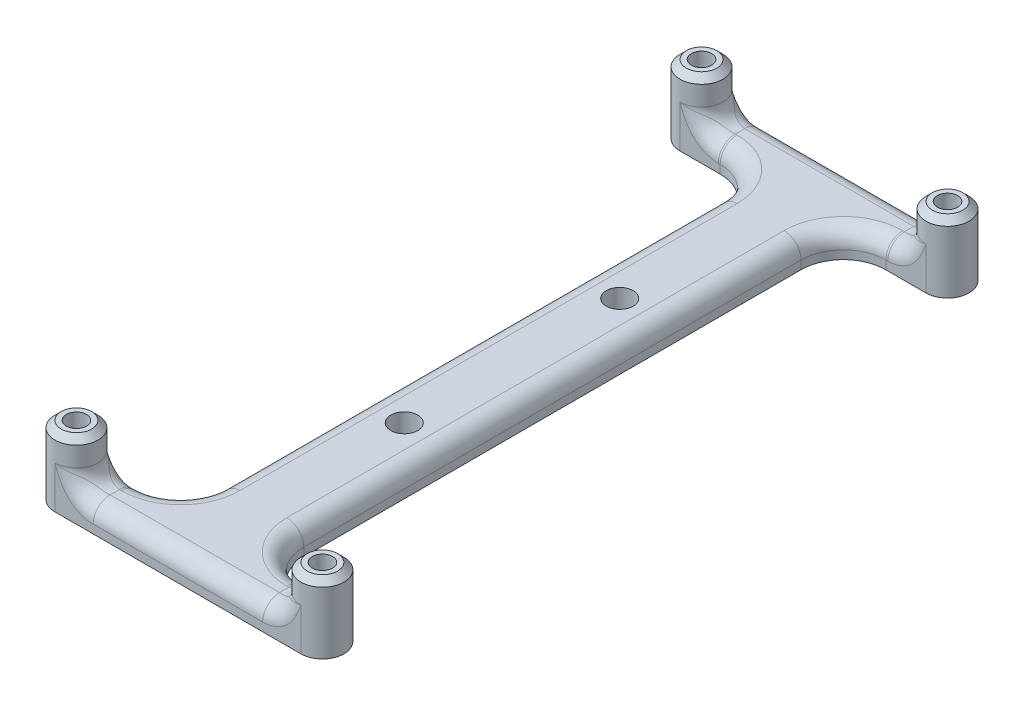
SolidWorks part; units mm, degrees
ref_plane "Front Plane" through (0, 0, 0) normal (0, 0, 1) x (1, 0, 0)
ref_plane "Top Plane" through (0, 0, 0) normal (0, 1, 0) x (1, 0, 0)
ref_plane "Right Plane" through (0, 0, 0) normal (1, 0, 0) x (0, 0, -1)
sketch "Sketch1" plane through (0, 0, 0) normal (0, 1, 0) x (1, 0, 0)
  line L1 (-4.7625, -34.305) -> (4.7625, -34.305)
  line L2 (-4.7625, -34.305) -> (-4.7625, 34.305)
  line L3 (-4.7625, 34.305) -> (4.7625, 34.305)
  line L4 (4.7625, -34.305) -> (4.7625, 34.305)
  line L5 (-4.7625, -34.305) -> (4.7625, 34.305) construction
  line L6 (-4.7625, 34.305) -> (4.7625, -34.305) construction
  line L7 (-14.5, 39.385) -> (14.5, 39.385)
  line L9 (-14.5, 34.305) -> (14.5, 34.305)
  line L11 (-14.5, 39.385) -> (14.5, 34.305) construction
  line L12 (-14.5, 34.305) -> (14.5, 39.385) construction
  line L13 (-14.5, -39.385) -> (14.5, -39.385)
  line L15 (-14.5, -34.305) -> (14.5, -34.305)
  line L17 (-14.5, -39.385) -> (14.5, -34.305) construction
  line L18 (-14.5, -34.305) -> (14.5, -39.385) construction
  arc A2 (-14.5, 34.305) -> (-14.5, 39.385) centre (-14.5, 36.845) cw
  arc A3 (14.5, 34.305) -> (14.5, 39.385) centre (14.5, 36.845) ccw
  arc A4 (-14.5, -39.385) -> (-14.5, -34.305) centre (-14.5, -36.845) cw
  arc A5 (14.5, -39.385) -> (14.5, -34.305) centre (14.5, -36.845) ccw
  point P0 (0, 0)
  point P6 (0, 36.845)
  point P11 (0, -36.845)
  point P17 (0, 0)
  point P18 (0, 0)
  point P19 (-14.1971, 41.0601)
  point P24 (13.1626, -36.2976)
  point P25 (0, 0)
  point P26 (13.1626, 40.1254)
  dimension "D4" = 29
  dimension "D1" = 9.525
  dimension "D2" = 5.08
  dimension "D3" = 5.08
  dimension "D5" = 73.69
extrude "Boss-Extrude1" add sketch "Sketch1" along normal blind 3 contours L13 A5 L15 L1 A4 | L1 L4 L3 L2 | L9 A3 L7 A2 L3 region at (0, 0, 0) region at (0, 0, 36.845) region at (0, 0, -36.845)
sketch "Sketch2" plane through (0, 3, 0) normal (0, 1, 0) x (1, 0, 0)
  line L0 (0, 12.7) -> (0, -12.7) construction
  circle A0 centre (0, 12.7) radius 1.5875
  circle A1 centre (0, -12.7) radius 1.5875
  dimension "D2" = 3.175
  dimension "D3" = 3.175
  dimension "D1" = 25.4
extrude "Cut-Extrude1" cut sketch "Sketch2" against normal through all
sketch "Sketch3" plane through (0, 3, 0) normal (0, 1, 0) x (1, 0, 0)
  circle A0 centre (-14.5, 36.845) radius 2.54
  circle A1 centre (14.5, 36.845) radius 2.54
  circle A2 centre (14.5, -36.845) radius 2.54
  circle A3 centre (-14.5, -36.845) radius 2.54
  arc A4 (-14.5, 39.385) -> (-14.5, 34.305) centre (-14.5, 36.845) ccw construction
  arc A5 (14.5, 34.305) -> (14.5, 39.385) centre (14.5, 36.845) ccw construction
  arc A6 (-14.5, -34.305) -> (-14.5, -39.385) centre (-14.5, -36.845) ccw construction
  arc A7 (14.5, -39.385) -> (14.5, -34.305) centre (14.5, -36.845) ccw construction
extrude "Boss-Extrude2" add sketch "Sketch3" along normal blind 5.08
sketch "Sketch4" plane through (0, 8.08, 0) normal (0, 1, 0) x (1, 0, 0)
  circle A0 centre (-14.5, 36.845) radius 1.1938
  circle A1 centre (14.5, 36.845) radius 1.1938
  circle A2 centre (14.5, -36.845) radius 1.1938
  circle A3 centre (-14.5, -36.845) radius 1.1938
  dimension "D1" = 2.3876
  dimension "D2" = 2.3876
  dimension "D3" = 2.3876
  dimension "D4" = 2.3876
extrude "Cut-Extrude2" cut sketch "Sketch4" against normal blind 3.2004
sketch "Sketch5" plane through (0, 4.8796, 0) normal (0, 1, 0) x (1, 0, 0)
  circle A0 centre (-14.5, 36.845) radius 0.875
  circle A1 centre (14.5, 36.845) radius 0.875
  circle A2 centre (14.5, -36.845) radius 0.875
  circle A3 centre (-14.5, -36.845) radius 0.875
  dimension "D1" = 1.75
  dimension "D2" = 1.75
  dimension "D3" = 1.75
  dimension "D4" = 1.75
extrude "Cut-Extrude3" cut sketch "Sketch5" against normal through all
chamfer "Chamfer1" distance 0.75 angle 45 4 edges at (-14.5, 8.08, -34.305) (14.5, 8.08, -34.305) (14.5, 8.08, 39.385) (-14.5, 8.08, 39.385)
fillet "Fillet1" radius 5 4 edges at (-4.7625, 1.5, -34.305) (4.7625, 1.5, -34.305) (-4.7625, 1.5, 34.305) (4.7625, 1.5, 34.305)
fillet "Fillet2" radius 2 4 edges at (-11.96, 3, 36.845) (11.96, 3, 36.845) (11.96, 3, -36.845) (-11.96, 3, -36.845)
fillet "Fillet3" radius 2 20 edges at (-11.737, 3.1613, -39.385) (11.737, 3.1613, -39.385) (-11.737, 3.1613, 39.385) (11.737, 3.1613, 39.385) (11.737, 3.1613, 34.305) (-10.2498, 3, 34.305) (11.737, 3.1613, -34.305) (-10.2498, 3, -34.305) (6.227, 3, -32.8405) (4.7625, 3, 0) (-11.737, 3.1613, -34.305) (10.2498, 3, -34.305) (-6.227, 3, -32.8405) (-4.7625, 3, 0) (-11.737, 3.1613, 34.305) (10.2498, 3, 34.305) (0, 3, -39.385) (0, 3, 39.385) (6.227, 3, 32.8405) (-6.227, 3, 32.8405)
